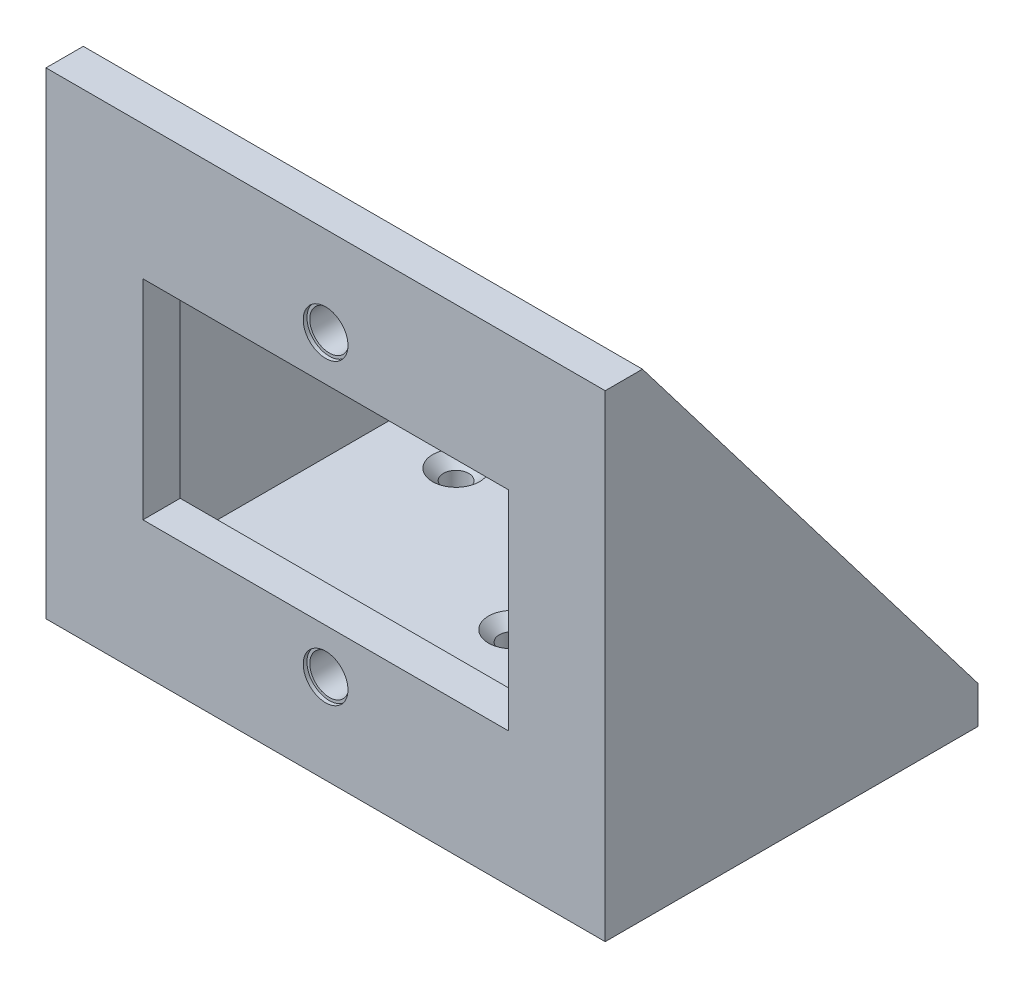
SolidWorks part; units mm, degrees
ref_plane "Front Plane" through (0, 0, 0) normal (0, 0, 1) x (1, 0, 0)
ref_plane "Top Plane" through (0, 0, 0) normal (0, 1, 0) x (1, 0, 0)
ref_plane "Right Plane" through (0, 0, 0) normal (1, 0, 0) x (0, 0, -1)
sketch "Sketch1" plane through (0, 0, 0) normal (0, 1, 0) x (1, 0, 0)
  line L1 (-37.5, 25) -> (37.5, 25)
  line L2 (-37.5, 25) -> (-37.5, -25)
  line L3 (-37.5, -25) -> (37.5, -25)
  line L4 (37.5, 25) -> (37.5, -25)
  line L5 (-37.5, 25) -> (37.5, -25) construction
  line L6 (-37.5, -25) -> (37.5, 25) construction
  point P0 (0, 0)
  dimension "D1" = 50
  dimension "D2" = 75
extrude "Boss-Extrude1" add sketch "Sketch1" along normal blind 5
sketch "Sketch2" plane through (0, 0, 25) normal (0, 0, 1) x (1, 0, 0)
  line L14 (-24.5, 18) -> (24.5, 46) construction
  line L15 (-24.5, 46) -> (24.5, 18) construction
  line L16 (0, 0) -> (0, 64) construction
  line L17 (37.5, 0) -> (-37.5, 0)
  line L18 (37.5, 0) -> (37.5, 64)
  line L19 (37.5, 64) -> (-37.5, 64)
  line L20 (-37.5, 0) -> (-37.5, 64)
  line L21 (37.5, 0) -> (-37.5, 64) construction
  line L22 (37.5, 64) -> (-37.5, 0) construction
  point P4 (0, 32)
  point P11 (0, 32)
  line B0 (-27.377, 16.3398) -> (-1.377, 6.8065)
  line B1 (1.377, 6.8065) -> (27.377, 16.3398)
  line B2 (30, 20.0953) -> (30, 43.9047)
  line B3 (27.377, 47.6602) -> (1.377, 57.1935)
  line B4 (-1.377, 57.1935) -> (-27.377, 47.6602)
  line B5 (-30, 43.9047) -> (-30, 20.0953)
  line B6 (24.5, 18) -> (24.5, 46)
  line B7 (24.5, 46) -> (-24.5, 46)
  line B8 (-24.5, 46) -> (-24.5, 18)
  line B9 (-24.5, 18) -> (24.5, 18)
  circle B10 centre (0, 12) radius 1.3
  circle B11 centre (0, 52) radius 1.3
  arc B12 (-30, 20.0953) -> (-27.377, 16.3398) centre (-26, 20.0953) ccw
  arc B13 (-1.377, 6.8065) -> (1.377, 6.8065) centre (0, 10.562) ccw
  arc B14 (27.377, 16.3398) -> (30, 20.0953) centre (26, 20.0953) ccw
  arc B15 (30, 43.9047) -> (27.377, 47.6602) centre (26, 43.9047) ccw
  arc B16 (1.377, 57.1935) -> (-1.377, 57.1935) centre (0, 53.438) ccw
  arc B17 (-27.377, 47.6602) -> (-30, 43.9047) centre (-26, 43.9047) ccw
  line M23 (37.5, 5) -> (-37.5, 5)
  dimension "D1" = 32
sketch_block_instance "Block1-1"
sketch_block "Block1"
extrude "Boss-Extrude2" add sketch "Sketch2" against normal blind 5 contours L20 L18 L19 B17 B4 B16 B3 B15 B2 B14 B1 B13 B0 B12 B5 M23 | B4 B17 B5 B12 B0 B13 B1 B14 B2 B15 B3 B16 B9 B8 B7 B6 B10 B11 | B11 | B10 region at (0, 5.9543, 25) region at (-28.6344, 18.2553, 25) region at (0, 52, 25)
sketch "Sketch3" plane through (37.5, 0, 0) normal (1, 0, 0) x (0, 0, -1)
  line L0 (-20, 64) -> (25, 5)
  line L1 (25, 5) -> (-20, 5)
  line L2 (-20, 5) -> (-20, 64)
extrude "Boss-Extrude3" add sketch "Sketch3" against normal blind 5
extrude "Boss-Extrude4" add sketch "Sketch3<2>" along normal blind 5 from surface starting at face at (-37.5, 23, 6.6667)
sketch "Sketch3<2>" plane through (37.5, 0, 0) normal (1, 0, 0) x (0, 0, -1) same geometry as "Sketch3"
sketch "Sketch4" plane through (0, 0, 25) normal (0, 0, 1) x (1, 0, 0)
  point P0 (0, 52)
  point P1 (0, 12)
hole_wizard "CBORE for M3 SHCS1" positions "Sketch4" profile "Sketch5" counterbore size "M3" standard "ANSI Metric"
sketch "Sketch5" plane through (0, 52, 25) normal (1, 0, 0) x (0, -1, 0)
  line L0 (0, 0) -> (0, 6.5773)
  line L1 (0, 6.5773) -> (2.625, 5)
  line L2 (2.625, 5) -> (2.625, 0.5)
  line L3 (2.625, 0.5) -> (3, 0.5)
  line L4 (3, 0.5) -> (3, 0)
  line L5 (3, 0) -> (0, 0)
  line L10 (0, 6.5773) -> (-2.625, 5) construction
  line L11 (0, -6.35) -> (0, 107.95) construction
  dimension "Hole Dia." = 5.25
  dimension "Hole Depth" = 5
  dimension "C'Bore Dia." = 6
  dimension "C'Bore Depth" = 0.5
  dimension "Drill Angle" = 118
sketch "Sketch6" plane through (0, 5, 0) normal (0, 1, 0) x (1, 0, 0)
  line L1 (-22.5, 15) -> (22.5, 15)
  line L2 (-22.5, 15) -> (-22.5, -15)
  line L3 (-22.5, -15) -> (22.5, -15)
  line L4 (22.5, 15) -> (22.5, -15)
  line L5 (-22.5, 15) -> (22.5, -15) construction
  line L6 (-22.5, -15) -> (22.5, 15) construction
  point P0 (0, 0)
  point P6 (0, 0)
  point P7 (-22.5, 15)
  point P8 (-22.5, -15)
  point P9 (22.5, -15)
  point P10 (22.5, 15)
  dimension "D1" = 30
  dimension "D2" = 45
hole_wizard "CSK for M3 Flat Head Machine Screw1" positions "Sketch6" profile "Sketch8" countersink size "M3" standard "ANSI Metric" end condition through all
sketch "Sketch8" plane through (22.5, 5, -15) normal (1, 0, 0) x (0, 0, 1)
  line L0 (0, 0) -> (0, 5)
  line L1 (0, 5) -> (1.7, 5)
  line L2 (1.7, 5) -> (1.7, 1.45)
  line L3 (1.7, 1.45) -> (3.15, 0)
  line L5 (3.15, 0) -> (0, 0)
  line L6 (-1.7, 1.45) -> (-3.15, 0) construction
  line L11 (0, -6.35) -> (0, 107.95) construction
  dimension "Thru Hole Dia." = 3.4
  dimension "Thru Hole Depth" = 5
  dimension "Near C'Sink Dia." = 6.3
  dimension "Near C'Sink Angle" = 90
